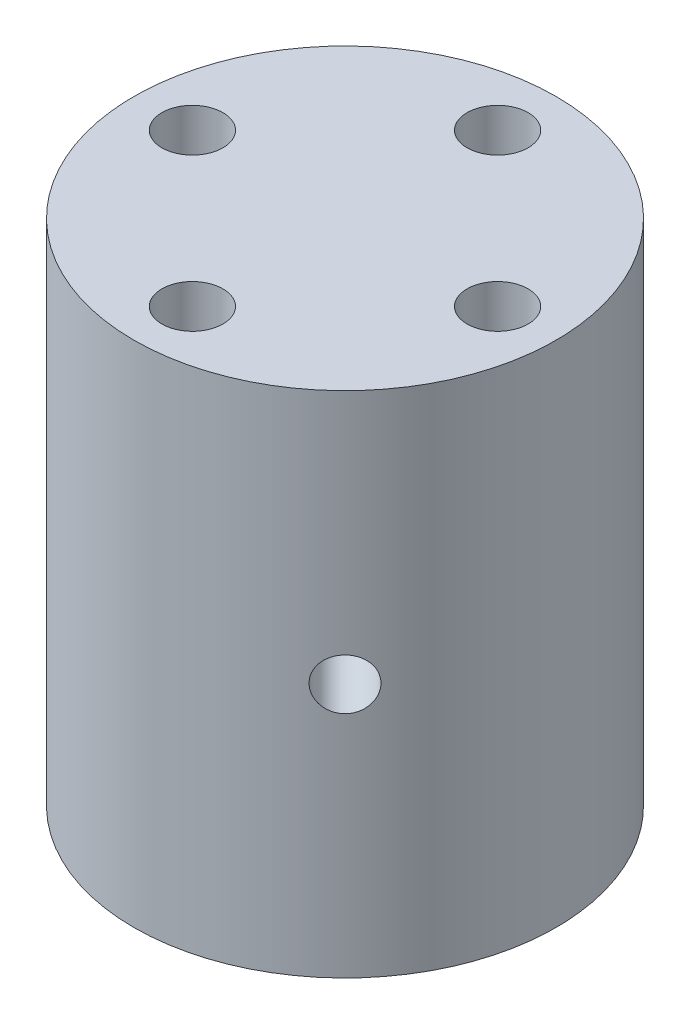
SolidWorks part; units mm, degrees
ref_plane "Front" through (0, 0, 0) normal (0, 0, 1) x (1, 0, 0)
ref_plane "Top" through (0, 0, 0) normal (0, 1, 0) x (1, 0, 0)
ref_plane "Right" through (0, 0, 0) normal (1, 0, 0) x (0, 0, -1)
sketch "草图1" plane through (0, 0, 0) normal (0, 1, 0) x (1, 0, 0)
  circle A0 centre (0, 0) radius 10.375
  dimension "D1" = 20.75
extrude "凸台-拉伸1" add sketch "草图1" along normal blind 25
sketch "草图2" plane through (0, 25, 0) normal (0, 1, 0) x (1, 0, 0)
  line L0 (0, 10.375) -> (0, -10.375) construction
  line L1 (-10.375, 0) -> (10.375, 0) construction
  circle A0 centre (0, 0) radius 10.375 construction
  circle A1 centre (0, 7.5) radius 1.5
  circle A2 centre (-7.5, 0) radius 1.5
  circle A3 centre (7.5, 0) radius 1.5
  circle A4 centre (0, -7.5) radius 1.5
  dimension "D2" = 15
  dimension "D3" = 15
extrude "切除-拉伸1" cut sketch "草图2" against normal through all
ref_axis "基准轴1" through (0, -50, 0) along (0, 1, 0)
ref_plane "基准面1" through (0, 0, 0) normal (0.7071, 0, 0.7071) x (0, 1, 0)
sketch "草图3" plane through (0, 0, 0) normal (0.7071, 0, 0.7071) x (0, 1, 0)
  line L0 (25, 0) -> (0, 0) construction
  line L1 (25, -10.375) -> (25, 10.375) construction
  line L2 (0, 10.375) -> (0, -10.375) construction
  circle A0 centre (12.5, 0) radius 1.25
  dimension "D1" = 2.5
extrude "切除-拉伸2" cut sketch "草图3" against normal through all both and the other way through all
